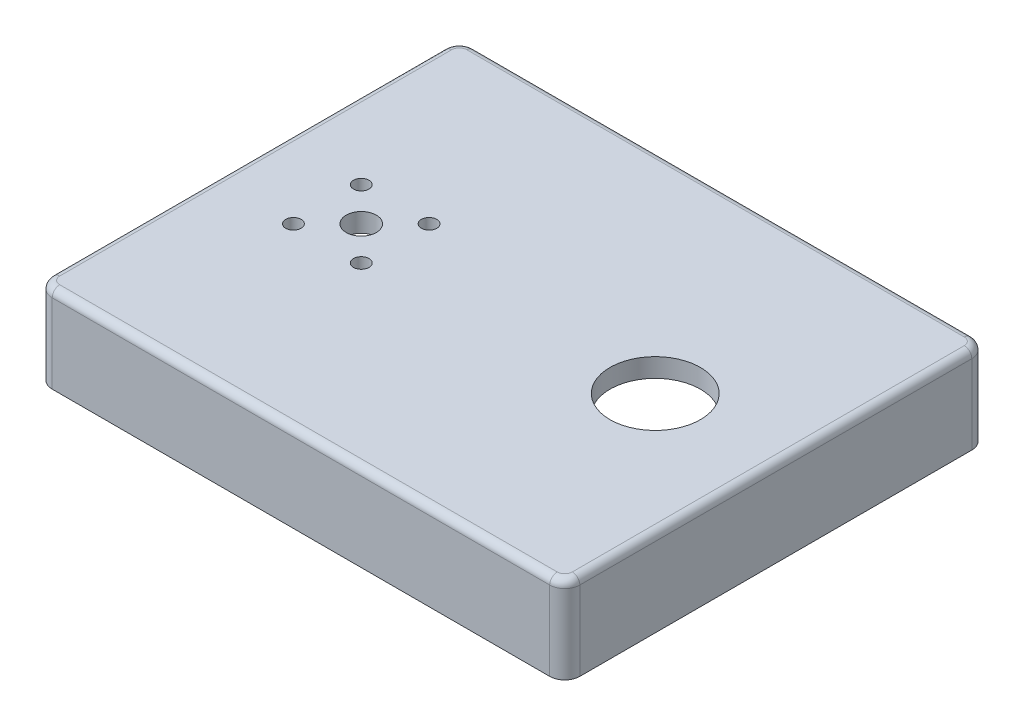
SolidWorks part; units mm, degrees
material "Teak"
ref_plane "Front Plane" through (0, 0, 0) normal (0, 0, 1) x (1, 0, 0)
ref_plane "Top Plane" through (0, 0, 0) normal (0, 1, 0) x (1, 0, 0)
ref_plane "Right Plane" through (0, 0, 0) normal (1, 0, 0) x (0, 0, -1)
sketch "Sketch2" plane through (0, 0, 0) normal (0, 1, 0) x (1, 0, 0)
  line L0 (104.775, -88.9) -> (-104.775, -88.9)
  line L1 (111.125, -82.55) -> (111.125, 82.55)
  line L2 (-111.125, -82.55) -> (-111.125, 82.55)
  line L3 (104.775, 88.9) -> (-104.775, 88.9)
  line L4 (-104.775, 82.55) -> (-101.6, 79.375) construction
  line L5 (101.6, 79.375) -> (104.775, 82.55) construction
  line L6 (-111.125, 0) -> (111.125, 0) construction
  line L7 (-63.5, 88.9) -> (-63.5, -88.9) construction
  line L8 (-107.95, -66.675) -> (-107.95, 66.7727)
  line L9 (101.6, -79.375) -> (104.775, -82.55) construction
  line L10 (-101.6, -79.375) -> (-104.775, -82.55) construction
  line L27 (88.9, 85.725) -> (-88.9977, 85.725)
  line L30 (88.9, -85.725) -> (-88.9, -85.725)
  line L33 (107.95, -66.675) -> (107.95, 66.675)
  circle A0 centre (-63.5, 0) radius 6.35
  circle A1 centre (-77.7875, 14.2875) radius 3.2639
  circle A2 centre (-49.2125, 14.2875) radius 3.2639
  circle A3 centre (-49.2125, -14.2875) radius 3.2639
  circle A4 centre (-77.7875, -14.2875) radius 3.2639
  circle A5 centre (60.325, 0) radius 19.05
  arc A6 (-104.775, -88.9) -> (-111.125, -82.55) centre (-104.775, -82.55) cw
  arc A7 (111.125, -82.55) -> (104.775, -88.9) centre (104.775, -82.55) cw
  arc A8 (111.125, 82.55) -> (104.775, 88.9) centre (104.775, 82.55) ccw
  arc A9 (-111.125, 82.55) -> (-104.775, 88.9) centre (-104.775, 82.55) cw
  arc A10 (95.25, 79.375) -> (101.6, 73.025) centre (101.6, 79.375) ccw
  circle A11 centre (-103.1875, -80.9625) radius 3.3734
  circle A12 centre (-103.1875, 80.9625) radius 3.3734
  arc A13 (101.6, -73.025) -> (95.25, -79.375) centre (101.6, -79.375) ccw
  arc A14 (-101.6, 73.1227) -> (-95.3477, 79.375) centre (-101.6, 79.375) ccw
  arc A15 (-101.6, 73.1227) -> (-107.95, 66.7727) centre (-101.6, 66.7727) ccw
  arc A16 (-95.3477, 79.375) -> (-88.9977, 85.725) centre (-88.9977, 79.375) cw
  circle A17 centre (103.1875, 80.9625) radius 3.3734
  circle A18 centre (103.1875, -80.9625) radius 3.3734
  arc A19 (-95.25, -79.375) -> (-101.6, -73.025) centre (-101.6, -79.375) ccw
  arc A20 (-95.25, -79.375) -> (-88.9, -85.725) centre (-88.9, -79.375) ccw
  arc A21 (-101.6, -73.025) -> (-107.95, -66.675) centre (-101.6, -66.675) cw
  arc A22 (95.25, -79.375) -> (88.9, -85.725) centre (88.9, -79.375) cw
  arc A23 (101.6, -73.025) -> (107.95, -66.675) centre (101.6, -66.675) ccw
  arc A24 (95.25, 79.375) -> (88.9, 85.725) centre (88.9, 79.375) ccw
  arc A25 (101.6, 73.025) -> (107.95, 66.675) centre (101.6, 66.675) cw
  circle A26 centre (-96.6912, -60.9442) radius 1.6844
  circle A27 centre (-98.3755, 0) radius 3.2259
  circle A28 centre (-96.6912, 67.7449) radius 2.6156
  circle A29 centre (-12.6422, 0) radius 3.1737
  circle A30 centre (-12.6422, -60.9442) radius 1.7438
  circle A31 centre (-12.6422, 67.7449) radius 3.2059
  point P1 (0, 0)
  dimension "D4" = 12.7
  dimension "D5" = 14.2875
  dimension "D13" = 6.5278
  dimension "D14" = 6.5278
  dimension "D15" = 6.5278
  dimension "D16" = 6.5278
  dimension "D17" = 38.1
  dimension "D19" = 6.35
  dimension "D23" = 6.7469
  dimension "D21" = 6.7469
  dimension "D22" = 6.7469
  dimension "D24" = 6.7469
  dimension "D2" = 222.25
  dimension "D3" = 47.625
  dimension "D6" = 14.2875
  dimension "D7" = 14.2875
  dimension "D8" = 14.2875
  dimension "D9" = 14.2875
  dimension "D10" = 14.2875
  dimension "D11" = 14.2875
  dimension "D12" = 14.2875
  dimension "D18" = 50.8
  dimension "D20" = 177.8
extrude "Boss-Extrude1" add sketch "Sketch2" against normal blind 28.575 contours L2 A9 L3 A8 L1 A7 L0 A6 | L8 A15 A14 A16 L27 A24 A10 A25 L33 A23 A13 A22 L30 A20 A19 A21 | A17 | A18 | A11 | A12
extrude "Boss-Extrude2" add sketch "Sketch2<3>" along normal blind 7.9375 contours A5 | L2 A9 L3 A8 L1 A7 L0 A6 | A4 | A0 | A1 | A2 | A3 region at (60.325, 0, 0)
sketch "Sketch2<3>" plane through (0, 0, 0) normal (0, 1, 0) x (1, 0, 0) same geometry as "Sketch2"
fillet "Fillet1" radius 3.175 8 edges at (-109.2651, 7.9375, 87.0401) (0, 7.9375, 88.9) (109.2651, 7.9375, 87.0401) (111.125, 7.9375, 0) (109.2651, 7.9375, -87.0401) (0, 7.9375, -88.9) (-109.2651, 7.9375, -87.0401) (-111.125, 7.9375, 0)
sketch "Sketch3" plane through (0, 0, 0) normal (0, 1, 0) x (1, 0, 0)
  line L0 (-100.8062, -61.5461) -> (-100.8062, 61.6439) construction
  line L1 (-100.8062, 61.6439) -> (-20.1612, 61.6439) construction
  line L2 (-20.1612, 61.6439) -> (-20.1612, -61.5461) construction
  line L3 (-20.1612, -61.5461) -> (-100.8062, -61.5461) construction
  line L4 (-100.8062, 0.0489) -> (-20.1612, 0.0489) construction
  line L5 (-107.95, -66.675) -> (-107.95, 66.7727) construction
  circle A0 centre (-20.1612, 61.6439) radius 2.5794
  circle A1 centre (-20.1612, -61.5461) radius 2.5794
  circle A2 centre (-100.8062, -61.5461) radius 2.5794
  circle A3 centre (-100.8062, -33.6061) radius 2.5794
  circle A4 centre (-100.8062, 33.7039) radius 2.5794
  circle A5 centre (-100.8062, 61.6439) radius 2.5794
  circle A6 centre (-100.8062, -6.3011) radius 2.5794
  point P8 (-107.95, 0.0489)
  dimension "D4" = 5.1587
  dimension "D5" = 5.1587
  dimension "D6" = 5.1587
  dimension "D7" = 5.1587
  dimension "D8" = 5.1587
  dimension "D9" = 5.1587
  dimension "D12" = 5.1587
  dimension "D1" = 123.19
  dimension "D2" = 80.645
  dimension "D3" = 7.1437
  dimension "D10" = 27.94
  dimension "D11" = 27.94
  dimension "D13" = 6.35
extrude "Cut-Extrude1" cut sketch "Sketch3" along normal blind 4.7625 from surface starting at face at (-0.0135, 0, -0.0135)
